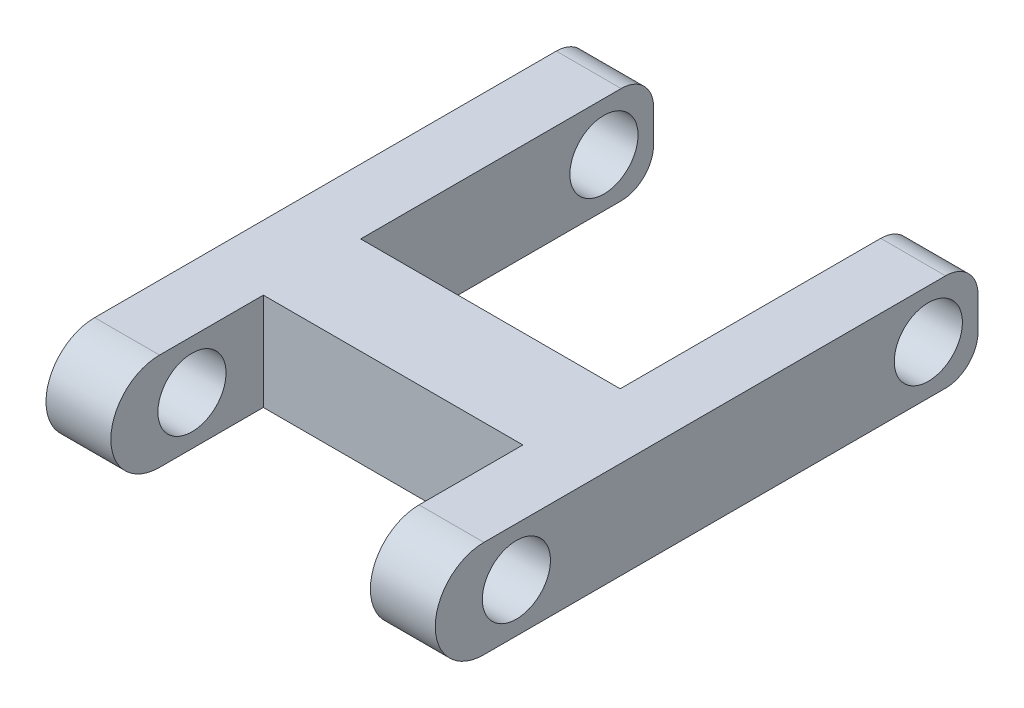
SolidWorks part; units mm, degrees
ref_plane "前视基准面" through (0, 0, 0) normal (0, 0, 1) x (1, 0, 0)
ref_plane "上视基准面" through (0, 0, 0) normal (0, 1, 0) x (1, 0, 0)
ref_plane "右视基准面" through (0, 0, 0) normal (1, 0, 0) x (0, 0, -1)
other "Configuration Table"
sketch "草图1" plane through (0, 0, 0) normal (0, 1, 0) x (1, 0, 0)
  line L0 (-6, 0) -> (6, 0)
  line L1 (-6, 0) -> (-6, -8.7)
  line L2 (-6, -8.7) -> (-4, -8.7)
  line L3 (-4, -8.7) -> (-4, -3)
  line L4 (-4, -3) -> (4, -3)
  line L5 (4, -3) -> (4, -8.7)
  line L6 (4, -8.7) -> (6, -8.7)
  line L7 (6, -8.7) -> (6, 0)
  point P4 (0, 0)
  dimension "D1" = 8.7
  dimension "D2" = 2
  dimension "D3" = 5.7
  dimension "D4" = 8
  dimension "D5" = 5.7
  dimension "D6" = 5.7
  dimension "D7" = 6
extrude "凸台-拉伸1" add sketch "草图1" along normal blind 3
sketch "草图2" plane through (-6, 0, 0) normal (-1, 0, 0) x (0, 0, 1)
  line L0 (0, 3) -> (8.7, 3) construction
  line L2 (6.2, 3) -> (0, 3)
  line L3 (0, 3) -> (0, 0)
  line L4 (0, 0) -> (6.2, 0)
  arc A0 (6.2, 0) -> (6.2, 3) centre (6.2, 1.5) ccw
  dimension "D2" = 6.2
  dimension "D1" = 1.5
  dimension "D3" = 3
extrude "切除-拉伸1" cut sketch "草图2" against normal blind 12 flip side to cut
sketch "草图3" plane through (-6, 0, 0) normal (-1, 0, 0) x (0, 0, 1)
  line L0 (6.2, 1.5) -> (5.2, 1.5) construction
  circle A2 centre (5.2, 1.5) radius 1.05
  dimension "D3" = 2.1
  dimension "D2" = 1
extrude "切除-拉伸2" cut sketch "草图3" against normal blind 12
fillet "圆角1" radius 1 2 edges at (6, 1.5, 0) (-6, 1.5, 0)
sketch "草图4" plane through (0, 0, 0) normal (0, 0, -1) x (-1, 0, 0)
  line L0 (0, 3) -> (0, 0) construction
  line L1 (-5, 3) -> (5, 3) construction
  circle A0 centre (0, 1.5) radius 0.95
  dimension "D1" = 1.9
extrude "凸台-拉伸2" add sketch "草图4" along normal blind 4
ref_plane "基准面1" through (0, 0, -4) normal (0, 0, -1) x (-1, 0, 0)
sketch "草图5" plane through (0, 0, -4) normal (0, 0, -1) x (-1, 0, 0)
  line L3 (-6, 3) -> (-6, 0)
  line L15 (-6, 0) -> (6, 0)
  line L16 (6, 0) -> (6, 3)
  line L17 (6, 3) -> (-6, 3)
extrude "凸台-拉伸3" add sketch "草图5" along normal blind 8
sketch "草图6" plane through (6, 0, 0) normal (1, 0, 0) x (0, 0, -1)
  line L0 (12, 1.5) -> (7.5, 1.5) construction
  line L1 (12, 3) -> (12, 0) construction
  circle A1 centre (7.5, 1.5) radius 1.05
  dimension "D3" = 2.1
  dimension "D1" = 4.5
extrude "切除-拉伸3" cut sketch "草图6" against normal blind 12
sketch "草图8" plane through (0, 3, 0) normal (0, 1, 0) x (1, 0, 0)
  line L0 (-1.5, 8) -> (1.5, 8)
  line L1 (-1.5, 12) -> (-4, 12)
  line L2 (-6, 12) -> (6, 12) construction
  line L7 (-1.5, 12) -> (1.5, 12)
  line L8 (-4, 12) -> (-4, 8)
  line L12 (-4, 8) -> (-1.5, 8)
  line L13 (1.5, 8) -> (4, 8)
  line L14 (4, 8) -> (4, 12)
  line L15 (4, 12) -> (1.5, 12)
  dimension "D1" = 2.5
  dimension "D2" = 2.5
  dimension "D3" = 4
  dimension "D4" = 8
  dimension "D5" = 3
  dimension "D6" = 4
  dimension "D7" = 1.5
extrude "切除-拉伸4" cut sketch "草图8" against normal through all
fillet "圆角2" radius 1 2 edges at (5, 0, -12) (-5, 0, -12)
sketch "草图9" plane through (0, 0, -4) normal (0, 0, 1) x (1, 0, 0)
  line L4 (-6, 3) -> (-5.9, 3) construction
  line L5 (-6, 3) -> (6, 3) construction
  line L6 (6, 3) -> (5.9, 3) construction
  line L7 (-5.9, 3) -> (5.9, 3)
  line L8 (5.9, 3) -> (5.9, 0)
  line L9 (6, 0) -> (-6, 0) construction
  line L10 (5.9, 0) -> (-5.9, 0)
  line L11 (-5.9, 0) -> (-5.9, 3)
  dimension "D1" = 0.1
  dimension "D2" = 0.1
extrude "凸台-拉伸4" add sketch "草图9" along normal up to surface (4 mm away) up to face at (0.95, 1.5, 0)
sketch "草图10" plane through (0, 3, 0) normal (0, 1, 0) x (1, 0, 0)
  line L0 (-4, 8) -> (-4, 4)
  line L1 (-4, 4) -> (4, 4)
  line L2 (4, 4) -> (4, 8)
  line L3 (4, 8) -> (-4, 8)
  line L4 (-4, 12) -> (-4, 8) construction
  dimension "D1" = 4
extrude "切除-拉伸5" cut sketch "草图10" against normal blind 10
sketch "草图12" plane through (0, 0, -4) normal (0, 0, 1) x (1, 0, 0)
  line L0 (-6, 3) -> (6, 3)
  line L1 (6, 3) -> (6, 0)
  line L2 (6, 0) -> (6, 3) construction
  line L3 (6, 0) -> (-6, 0)
  line L4 (-6, 0) -> (-6, 3)
extrude "凸台-拉伸5" add sketch "草图12" along normal blind 2
fillet "圆角3" radius 1 2 edges at (6, 1.5, -2) (-6, 1.5, -2)
sketch "草图13" plane through (0, 0, 0) normal (0, -1, 0) x (1, 0, 0)
  line L0 (-6, -11) -> (-6, -2.4359) construction
  line L1 (-6, -9.0302) -> (6, -9.0302)
  line L2 (-6, -9.0302) -> (-6, -12)
  line L3 (-6, -12) -> (6, -12)
  line L4 (6, -9.0302) -> (6, -12)
  dimension "D1" = 9.0302
extrude "切除-拉伸6" cut sketch "草图13" against normal through all
fillet "圆角4" radius 1 4 edges at (5, 3, -9.0302) (5, 0, -9.0302) (-5, 3, -9.0302) (-5, 0, -9.0302)
sketch "草图15" plane through (0, 0, 0) normal (0, -1, 0) x (1, 0, 0)
  line L0 (-4, -8.0302) -> (-4, -4) construction
  line L1 (4, -4) -> (-4, -4)
  line L2 (4, -4) -> (4, 0)
  line L3 (4, 0) -> (-4, 0)
  line L4 (-4, -4) -> (-4, 0)
  dimension "D1" = 4
extrude "切除-拉伸7" cut sketch "草图15" against normal through all contours L3 L4 L1 L2
sketch "草图16" plane through (0, 0, 0) normal (0, -1, 0) x (1, 0, 0)
  line L0 (-6, 1) -> (-6, 6.2) construction
  line L1 (-6, 2.0556) -> (-4, 2.0556)
  line L2 (-6, 2.0556) -> (-6, -2.5404)
  line L3 (-6, -2.5404) -> (-4, -2.5404)
  line L4 (-4, 2.0556) -> (-4, -2.5404)
  line L5 (-4, -8.0302) -> (-4, 0) construction
  line L6 (6, 6.2) -> (6, 1) construction
  line L7 (6, 2.0556) -> (4, 2.0556)
  line L8 (6, 2.0556) -> (6, -2.5404)
  line L9 (6, -2.5404) -> (4, -2.5404)
  line L10 (4, 2.0556) -> (4, -2.5404)
  line L11 (4, 0) -> (4, -8.0302) construction
  dimension "D1" = 2.5404
  dimension "D2" = 2.0556
extrude "凸台-拉伸6" add sketch "草图16" against normal through all
